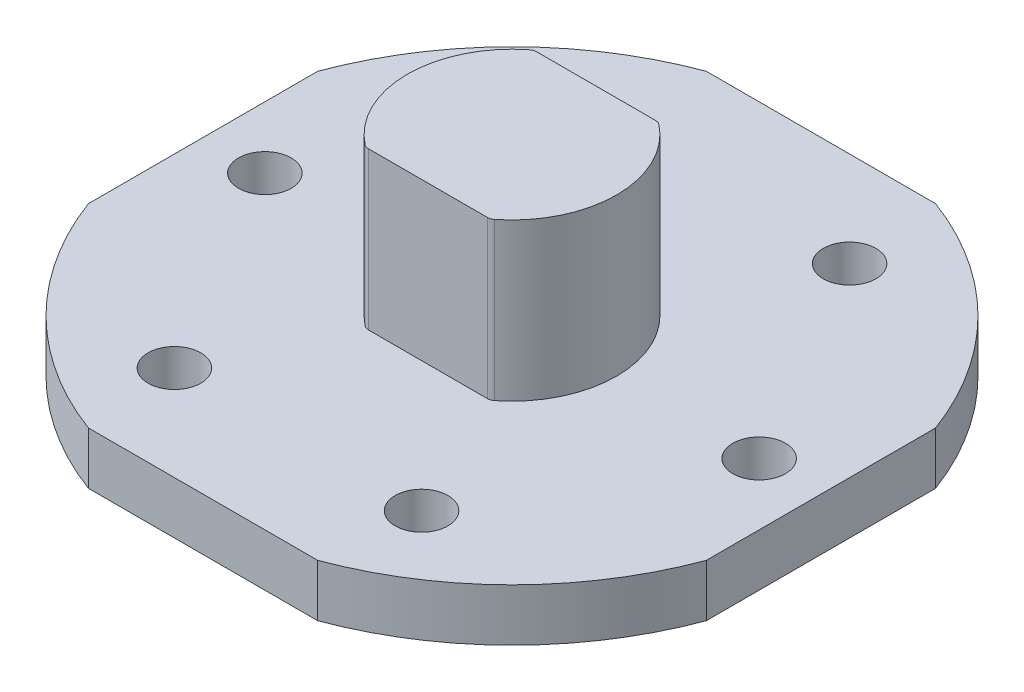
SolidWorks part; units mm, degrees
material "6061 Alloy"
ref_plane "Front Plane" through (0, 0, 0) normal (0, 0, 1) x (1, 0, 0)
ref_plane "Top Plane" through (0, 0, 0) normal (0, 1, 0) x (1, 0, 0)
ref_plane "Right Plane" through (0, 0, 0) normal (1, 0, 0) x (0, 0, -1)
sketch "Sketch1" plane through (0, 0, 0) normal (0, 1, 0) x (1, 0, 0)
  line L0 (-7.5664, 10.2) -> (7.5664, 10.2)
  line L1 (-7.5664, -10.2) -> (7.5664, -10.2)
  line L2 (-13.9194, 37.5) -> (13.9194, 37.5)
  line L3 (-37.5, 13.9194) -> (-37.5, -13.9194)
  line L4 (-13.9194, -37.5) -> (13.9194, -37.5)
  line L5 (37.5, 13.9194) -> (37.5, -13.9194)
  arc A0 (-7.5664, 10.2) -> (-7.5664, -10.2) centre (0, 0) ccw
  arc A1 (7.5664, -10.2) -> (7.5664, 10.2) centre (0, 0) ccw
  circle A2 centre (0, 0) radius 40
  circle A3 centre (0, 0) radius 30 construction
  circle A4 centre (-30, 0) radius 3 construction
  circle A5 centre (-15, 25.9808) radius 3 construction
  circle A6 centre (15, 25.9808) radius 3 construction
  circle A7 centre (30, 0) radius 3 construction
  circle A8 centre (15, -25.9808) radius 3 construction
  circle A9 centre (-15, -25.9808) radius 3 construction
  circle A10 centre (0, 0) radius 20 construction
  point P19 (0, 0)
  dimension "D1" = 12.7
  dimension "D3" = 80
  dimension "D4" = 60
  dimension "D6" = 6
  dimension "D7" = 40
  dimension "D2" = 20.4
  dimension "D8" = 75
  dimension "D5" = 6
extrude "Boss-Extrude1" add sketch "Sketch1" along normal blind 19.05 contours L1 A0 L0 region at (0, 0, 0)
extrude "Boss-Extrude2" add sketch "Sketch1<4>" against normal blind 6.35 contours L4 A2 L5 L2 L3 A1 L1 A0 L0 | L0 A1 L1 A0 region at (0, 0, -36.4393)
sketch "Sketch1<4>" plane through (0, 0, 0) normal (0, 1, 0) x (1, 0, 0) same geometry as "Sketch1"
hole_wizard "M6 Clearance Hole1" positions "3DSketch1" profile "Sketch2" hole size "M6" standard "ANSI Metric" end condition up to next
sketch3d "3DSketch1"
  point P28 (-30, 0, 0)
  point P30 (-15, 0, -25.9808)
  point P32 (15, 0, -25.9808)
  point P34 (30, 0, 0)
  point P36 (15, 0, 25.9808)
  point P38 (-15, 0, 25.9808)
sketch "Sketch2" plane through (-30, 0, 0) normal (1, 0, 0) x (0, 0, 1)
  line L0 (0, 0) -> (0, 6.35)
  line L1 (0, 6.35) -> (3.2, 6.35)
  line L2 (3.2, 6.35) -> (3.2, 0)
  line L5 (3.2, 0) -> (0, 0)
  line L11 (0, -6.35) -> (0, 107.95) construction
  dimension "Thru Hole Dia." = 6.4
  dimension "Thru Hole Depth" = 6.35
fillet "Fillet1" radius 1 4 edges at (-7.5664, 9.525, -10.2) (7.5664, 9.525, -10.2) (-7.5664, 9.525, 10.2) (7.5664, 9.525, 10.2)
